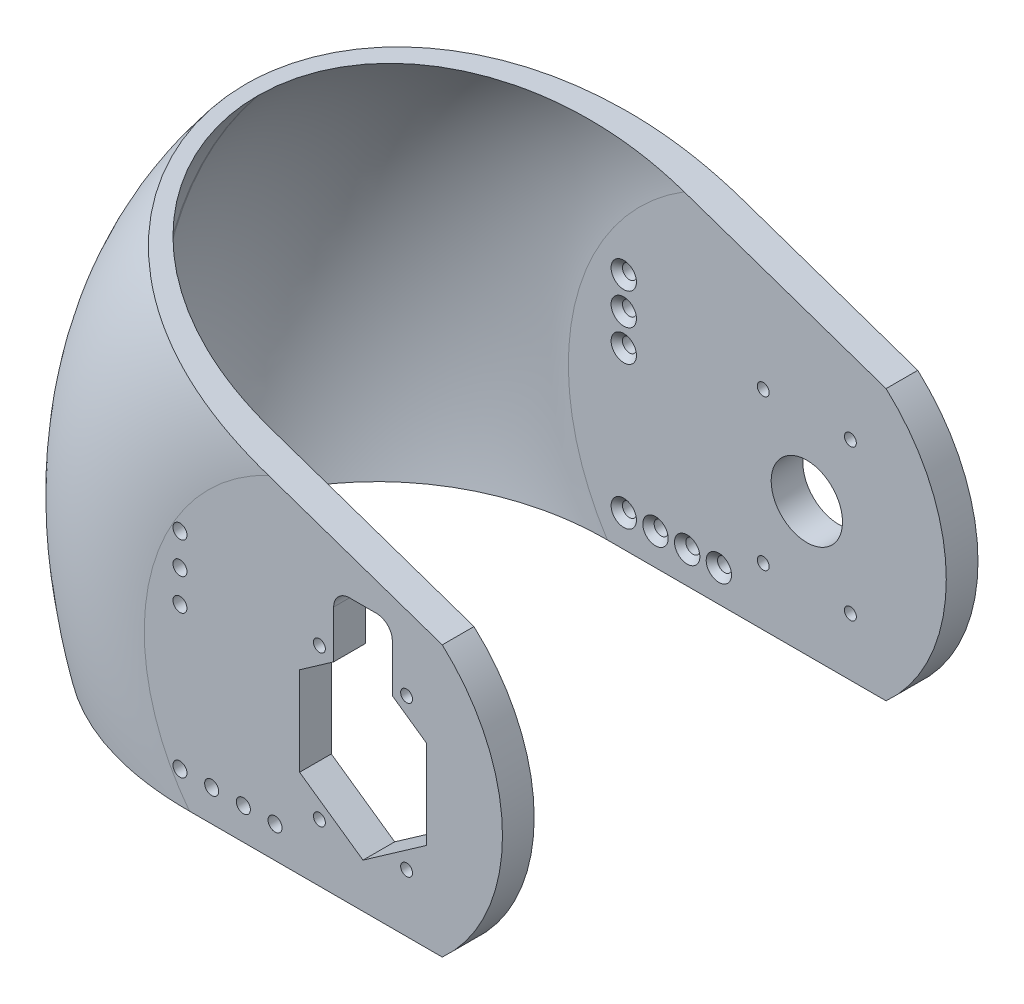
SolidWorks part; units mm, degrees
ref_plane "Front Plane" through (0, 0, 0) normal (0, 0, 1) x (1, 0, 0)
ref_plane "Top Plane" through (0, 0, 0) normal (0, 1, 0) x (1, 0, 0)
ref_plane "Right Plane" through (0, 0, 0) normal (1, 0, 0) x (0, 0, -1)
sketch "Sketch1" plane through (0, 0, 0) normal (0, 0, 1) x (1, 0, 0)
  line L0 (31.75, -53.34) -> (-174.9284, -53.34)
  line L2 (-142.2685, 114.912) -> (31.75, 54.9926)
  line L3 (31.75, 54.9926) -> (0, 0) construction
  line L4 (0, 0) -> (86.4977, 0) construction
  line L6 (-17.4625, 30.1625) -> (17.4625, 30.1625) construction
  line L7 (-17.4625, 30.1625) -> (-17.4625, -30.1625) construction
  line L8 (-17.4625, -30.1625) -> (17.4625, -30.1625) construction
  line L9 (17.4625, 30.1625) -> (17.4625, -30.1625) construction
  circle A0 centre (0, 0) radius 50.8 construction
  circle A1 centre (0, 0) radius 14.2875
  arc A4 (-142.2685, 114.912) -> (-174.9284, -53.34) centre (0, 0) ccw
  arc A10 (31.75, 54.9926) -> (31.75, -53.34) centre (-16.9805, 0.8263) cw
  circle A11 centre (-17.4625, 30.1625) radius 2.3813
  circle A12 centre (17.4625, 30.1625) radius 2.3813
  circle A13 centre (17.4625, -30.1625) radius 2.3813
  circle A14 centre (-17.4625, -30.1625) radius 2.3813
  circle A15 centre (-98.7284, -40.64) radius 2.3813 construction
  circle A16 centre (-86.0284, -40.64) radius 2.3813 construction
  circle A17 centre (-73.3284, -40.64) radius 2.3813 construction
  circle A18 centre (-60.6284, -40.64) radius 2.3812 construction
  circle A23 centre (-86.0284, 41.91) radius 2.3813 construction
  circle A24 centre (-86.0284, 29.21) radius 2.3813 construction
  circle A25 centre (-86.0284, 16.51) radius 2.3813 construction
  point P19 (0, 30.1625)
  point P21 (-17.4625, 0)
  point P32 (-179.529, 34.8489)
  point P35 (0, 0)
  point P36 (-86.1063, 43.7953)
  point P37 (-86.0284, 41.91)
  point P38 (55.88, 0.8263)
  point P39 (0, 0)
  point P40 (0, 0)
  point P41 (0, 0)
  dimension "D1" = 101.6
  dimension "D2" = 28.575
  dimension "D9" = 63.5
  dimension "D10" = 76.2
  dimension "D11" = 4
  dimension "D13" = 182.88
  dimension "D3" = 19
  dimension "D6" = 53.34
  dimension "D4" = 4.7625
  dimension "D5" = 12.7
  dimension "D7" = 55.88
  dimension "D16" = 4.7625
  dimension "D17" = 4.7625
  dimension "D8" = 60
  dimension "D12" = 12.7
  dimension "D14" = 60.325
  dimension "D15" = 34.925
  dimension "D18" = 12.7
  dimension "D19" = 12.7
  dimension "D20" = 57.15
extrude "Boss-Extrude1" add sketch "Sketch1" against normal blind 190.5
sketch "Sketch2" plane through (0, -53.34, 0) normal (0, -1, 0) x (1, 0, 0)
  line L0 (-182.88, 0) -> (-182.88, -190.5) construction
  line L1 (-182.88, -12.7) -> (55.88, -12.7)
  line L2 (-182.88, -12.7) -> (-182.88, -177.8)
  line L3 (-182.88, -177.8) -> (55.88, -177.8)
  line L6 (-174.9284, 0) -> (31.75, 0) construction
  line L7 (55.88, -190.5) -> (55.88, 0) construction
  line L8 (55.88, -12.7) -> (55.88, -177.8)
  line L9 (-182.88, 0) -> (-182.88, -190.5) construction
  point P6 (-192.8474, -167.8984)
  point P13 (0, 0)
  dimension "D1" = 165.1
  dimension "D2" = 12.7
extrude "Cut-Extrude1" cut sketch "Sketch2" against normal through all
sketch "Sketch3" plane through (0, 0, -177.8) normal (0, 0, 1) x (1, 0, 0)
  line L0 (-142.2685, 114.912) -> (-137.4653, 113.2581)
  line L2 (-174.9284, -53.34) -> (-169.8484, -53.34)
  line L3 (-174.9284, -53.34) -> (31.75, -53.34) construction
  arc A0 (-174.9284, -53.34) -> (-142.2685, 114.912) centre (0, 0) cw
  arc A1 (-142.2685, 114.912) -> (-174.9284, -53.34) centre (0, 0) ccw construction
  arc A2 (-169.8484, -53.34) -> (-137.4653, 113.2581) centre (2.2196, -0.34) cw
  point P14 (-179.529, 34.8489)
  point P15 (-174.518, 34.014)
  dimension "D1" = 5.08
  dimension "D2" = 5.08
  dimension "D3" = 5.08
  dimension "D4" = 19
extrude "Boss-Extrude2" add sketch "Sketch3" along normal up to next (165.1 mm away)
sketch "Sketch5" plane through (0, 0, 0) normal (0, 0, 1) x (1, 0, 0)
  line L0 (-25.4, 17.78) -> (-25.4, -17.78)
  line L1 (25.4, -17.78) -> (25.4, 17.78)
  line L2 (-25.4, -17.78) -> (0, -35.5653)
  line L4 (0, -35.5653) -> (25.4, -17.78)
  line L5 (25.4, 17.78) -> (11.7475, 27.3396)
  line L7 (-11.7475, 27.3396) -> (-25.4, 17.78)
  line L8 (-11.7475, 27.3396) -> (-11.7475, 46.3896)
  line L9 (-5.3975, 52.7396) -> (5.3975, 52.7396)
  line L10 (11.7475, 46.3896) -> (11.7475, 27.3396)
  arc A0 (-11.7475, 46.3896) -> (-5.3975, 52.7396) centre (-5.3975, 46.3896) cw
  arc A1 (5.3975, 52.7396) -> (11.7475, 46.3896) centre (5.3975, 46.3896) cw
  point P9 (-25.4, 0)
  point P16 (-11.7475, 52.7396)
  point P19 (11.7475, 52.7396)
  dimension "D8" = 6.35
  dimension "D1" = 125
  dimension "D2" = 35.56
  dimension "D3" = 50.8
  dimension "D4" = 125
  dimension "D5" = 23.495
  dimension "D6" = 125
  dimension "D7" = 25.4
extrude "Cut-Extrude3" cut sketch "Sketch5" against normal up to body
fillet "Fillet2" radius 82.296 2 edges at (-174.518, 34.014, -12.7) (-174.518, 34.014, -177.8)
fillet "Fillet3" radius 95.25 2 edges at (-179.529, 34.8489, -190.5) (-179.529, 34.8489, 0)
sketch "Sketch6" plane through (0, 0, 0) normal (0, 0, 1) x (1, 0, 0)
  line L0 (-69.526, -53.34) -> (31.75, -53.34) construction
  circle A0 centre (-73.3284, 41.91) radius 2.3813 construction
  circle A1 centre (-73.3284, 29.21) radius 2.3813 construction
  circle A2 centre (-73.3284, 16.51) radius 2.3813 construction
  circle A5 centre (-73.3284, -40.64) radius 2.3813 construction
  circle A6 centre (-60.6284, -40.64) radius 2.3812 construction
  circle A7 centre (-47.9284, -40.64) radius 2.3812 construction
  circle A8 centre (-35.2284, -40.64) radius 2.3812 construction
  point P0 (-73.3284, 41.91)
  point P2 (-73.3284, 29.21)
  point P4 (-73.3284, 16.51)
  point P12 (-73.3284, -40.64)
  point P14 (-60.6284, -40.64)
  point P22 (0, 0)
  point P23 (0, 0)
  point P24 (-98.7284, -40.64)
  point P25 (-98.7284, -40.64)
  point P26 (0, 0)
  point P27 (0, 0)
  point P31 (-60.6284, -40.64)
  point P32 (-73.3284, -40.64)
  point P37 (0, 0)
  point P38 (-67.1451, 16.51)
  dimension "D3" = 4.7625
  dimension "D5" = 92.3784
  dimension "D6" = 4.7625
  dimension "D1" = 12.7
  dimension "D2" = 12.7
  dimension "D4" = 69.85
  dimension "D7" = 12.7
  dimension "D8" = 12.7
  dimension "D9" = 12.7
  dimension "D10" = 12.7
sketch "Sketch15" plane through (0, 0, -12.7) normal (0, 0, -1) x (-1, 0, 0)
  line L2 (-31.75, -53.34) -> (79.9142, -53.34)
  line L3 (49.1236, 82.8396) -> (-31.75, 54.9926)
  line L4 (-31.75, -53.34) -> (79.9142, -53.34)
  line L5 (49.1236, 82.8396) -> (-31.75, 54.9926)
  circle A0 centre (73.3284, 29.21) radius 2.3813 construction
  circle A1 centre (73.3284, 29.21) radius 2.3813 construction
  arc A2 (79.9142, -53.34) -> (49.1236, 82.8396) centre (-2.2196, -0.34) ccw
  arc A3 (-31.75, 54.9926) -> (-31.75, -53.34) centre (16.9805, 0.8263) ccw
  arc A4 (79.9142, -53.34) -> (49.1236, 82.8396) centre (-2.2196, -0.34) ccw
  arc A5 (-31.75, 54.9926) -> (-31.75, -53.34) centre (16.9805, 0.8263) ccw
  point P2 (73.3284, 29.21)
  point P23 (73.3284, 41.91)
  point P26 (73.3284, 16.51)
  point P37 (60.6284, -40.64)
  point P74 (73.3284, -40.64)
  point P180 (47.9284, -40.64)
  point P183 (35.2284, -40.64)
  dimension "D1" = 0
hole_wizard "CSK for #10 Flat Head Machine Screw (100)12" positions "Sketch15" profile "Sketch17" countersink size "#10" standard "ANSI Inch" end condition through all
sketch "Sketch17" plane through (-35.2284, -40.64, -12.7) normal (1, 0, 0) x (0, 1, 0)
  line L0 (0, 0) -> (0, 21.3048)
  line L1 (0, 21.3048) -> (2.8067, 21.3048)
  line L2 (2.8067, 21.3048) -> (2.8067, 2.2733)
  line L3 (2.8067, 2.2733) -> (5.08, 0)
  line L5 (5.08, 0) -> (0, 0)
  line L6 (-2.8067, 2.2733) -> (-5.08, 0) construction
  line L11 (0, -6.35) -> (0, 107.95) construction
  dimension "Thru Hole Dia." = 5.6134
  dimension "Thru Hole Depth" = 21.3048
  dimension "Near C'Sink Dia." = 10.16
  dimension "Near C'Sink Angle" = 90
ref_plane "Plane1" through (0, 0, -95.25) normal (0, 0, -1) x (-1, 0, 0)
mirror "Mirror1" about plane through (0, 0, -95.25) normal (0, 0, -1) of "CSK for #10 Flat Head Machine Screw (100)12"
